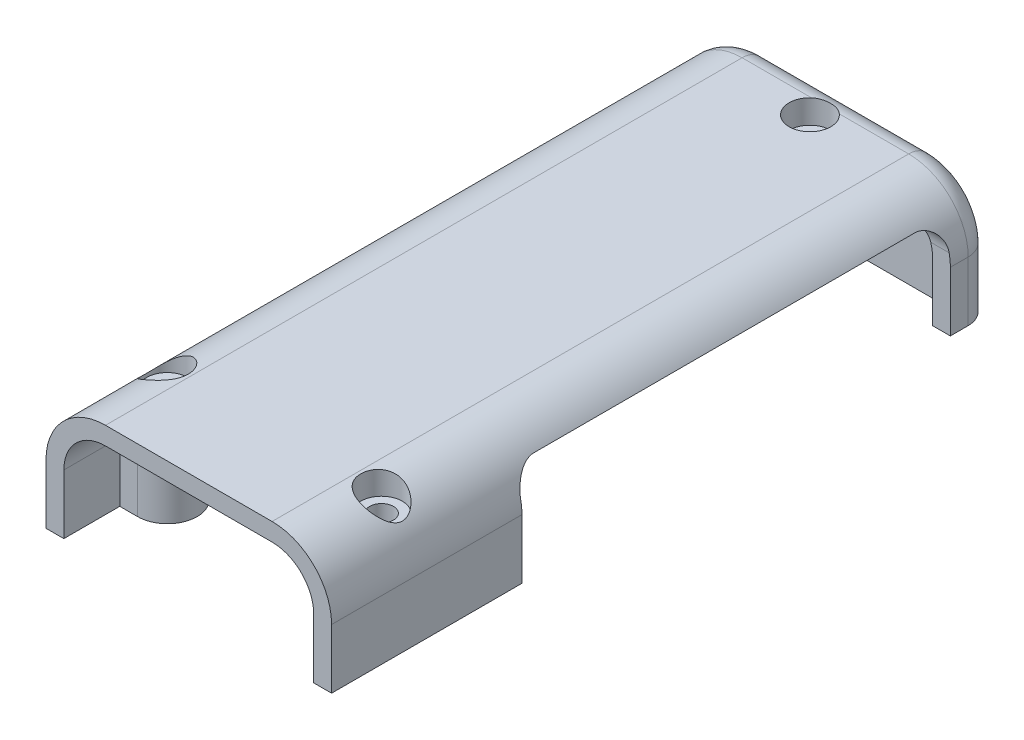
SolidWorks part; units mm, degrees
ref_plane "Front Plane" through (0, 0, 0) normal (0, 0, 1) x (1, 0, 0)
ref_plane "Top Plane" through (0, 0, 0) normal (0, 1, 0) x (1, 0, 0)
ref_plane "Right Plane" through (0, 0, 0) normal (1, 0, 0) x (0, 0, -1)
sketch "Sketch1" plane through (0, 0, 0) normal (0, 0, 1) x (1, 0, 0)
  line L0 (0, -24.4696) -> (0, 33.8552) construction
  line L1 (-46.7604, 0) -> (49.2743, 0) construction
  line L2 (10.5, 0) -> (10.5, 5)
  line L3 (12, 0) -> (12, 5)
  line L4 (-7, 8.5) -> (7, 8.5)
  line L5 (-7, 10) -> (7, 10)
  line L6 (9.2937, 5) -> (23.0317, 5) construction
  line L7 (7, 8.0974) -> (7, 12.4299) construction
  line L8 (10.5, 0) -> (12, 0)
  line L9 (-12, 0) -> (-12, 5)
  line L10 (-10.5, 0) -> (-12, 0)
  line L11 (-10.5, 0) -> (-10.5, 5)
  arc A0 (7, 8.5) -> (10.5, 5) centre (7, 5) cw
  arc A1 (7, 10) -> (12, 5) centre (7, 5) cw
  arc A2 (-7, 10) -> (-12, 5) centre (-7, 5) ccw
  arc A3 (-7, 8.5) -> (-10.5, 5) centre (-7, 5) ccw
  point P20 (0, 10)
  point P26 (0, 8.5)
  dimension "D4" = 5
  dimension "D1" = 12
  dimension "D2" = 1.5
  dimension "D3" = 10
extrude "Boss-Extrude1" add sketch "Sketch1" along normal blind 54
sketch "Sketch2" plane through (0, 0, 0) normal (0, 0, 1) x (1, 0, 0)
  line L0 (-12, 0) -> (12, 0)
  line L1 (12, 0) -> (12, 5)
  line L2 (7, 10) -> (-7, 10)
  line L3 (-12, 0) -> (-12, 5)
  arc A0 (-12, 5) -> (-7, 10) centre (-7, 5) cw
  arc A1 (12, 5) -> (7, 10) centre (7, 5) ccw
extrude "Boss-Extrude2" add sketch "Sketch2" against normal blind 1.5
sketch "Sketch3" plane through (12, 0, 0) normal (1, 0, 0) x (0, 0, -1)
  line L0 (-20, -2.8502) -> (-20, 11.6128) construction
  line L1 (-8, 0) -> (-2, 0)
  line L2 (-54, 0) -> (1.5, 0) construction
  line L3 (-2, 0) -> (-2, 6)
  line L4 (-36, 8) -> (-4, 8)
  line L5 (-38, 0) -> (-38, 6)
  line L6 (-8, 0) -> (-38, 0)
  arc A0 (-2, 6) -> (-4, 8) centre (-4, 6) ccw
  arc A1 (-38, 6) -> (-36, 8) centre (-36, 6) cw
  point P10 (-5.9016, 6.3989)
  point P11 (-8.3528, 0)
  point P14 (-20, 8)
  point P18 (-8, 0)
  dimension "D1" = 2
  dimension "D2" = 8
  dimension "D3" = 18
  dimension "D4" = 20
extrude "Cut-Extrude1" cut sketch "Sketch3" against normal blind 3
sketch "Sketch4" plane through (0, 0, 0) normal (0, -1, 0) x (1, 0, 0)
  line L0 (0, -5.1254) -> (0, 35.2905) construction
  line L1 (2.5, 0) -> (2.5, 1.8)
  line L2 (-10.5, 0) -> (10.5, 0) construction
  line L3 (-2.5, 0) -> (-2.5, 1.8)
  line L4 (-18.3062, 46.8) -> (17.3088, 46.8) construction
  line L5 (10.5, 49.3) -> (9, 49.3)
  line L6 (10.5, 54) -> (10.5, 38) construction
  line L7 (10.5, 49.3) -> (10.5, 44.3)
  line L8 (2.5, 0) -> (-2.5, 0)
  line L9 (10.5, 54) -> (10.5, 38) construction
  line L10 (10.5, 44.3) -> (9, 44.3)
  line L11 (-10.5, 49.3) -> (-10.5, 44.3)
  line L12 (-10.5, 44.3) -> (-9, 44.3)
  line L13 (-10.5, 49.3) -> (-9, 49.3)
  arc A0 (2.5, 1.8) -> (-2.5, 1.8) centre (0, 1.8) ccw
  arc A2 (9, 49.3) -> (9, 44.3) centre (9, 46.8) ccw
  arc A3 (-9, 49.3) -> (-9, 44.3) centre (-9, 46.8) cw
  point P11 (10.5, 46.8)
  point P19 (0, 0)
  dimension "D2" = 2.5
  dimension "D3" = 45
  dimension "D4" = 2.5
  dimension "D1" = 1.8
  dimension "D5" = 1.5
extrude "Boss-Extrude3" add sketch "Sketch4" against normal up to surface (8.5 mm away) up to face at (0, 8.5, 27)
sketch "Sketch5" plane through (0, 0, 0) normal (0, -1, 0) x (1, 0, 0)
  circle A0 centre (0, 1.8) radius 1
  circle A1 centre (9, 46.8) radius 1
  circle A2 centre (-9, 46.8) radius 1
  dimension "D1" = 2
extrude "Cut-Extrude2" cut sketch "Sketch5" against normal up to surface (10 mm away) up to face at (0, 10, 26.25)
sketch "Sketch6" plane through (0, 10, 0) normal (0, 1, 0) x (1, 0, 0)
  point P0 (0, -1.8)
  point P1 (-9, -46.8)
  point P3 (9, -46.8)
hole_wizard "Hole1" positions "Sketch7" profile "Sketch8" legacy end condition through all
sketch "Sketch7" plane through (0, 10, 0) normal (0, 1, 0) x (1, 0, 0)
  point P0 (0, -1.8)
  point P3 (-9, -46.8)
  point P6 (9, -46.8)
sketch "Sketch8" plane through (0, 10, 1.8) normal (1, 0, 0) x (0, 0, 1)
  line L0 (0, 0) -> (0, 10)
  line L1 (0, 10) -> (1, 10)
  line L2 (1, 10) -> (1, 2)
  line L3 (1, 2) -> (1.75, 2)
  line L4 (1.75, 2) -> (1.75, 0)
  line L5 (1.75, 0) -> (0, 0)
  line L6 (0, 110) -> (0, -10) construction
  dimension "Diameter" = 2
  dimension "Depth" = 10
  dimension "C-Bore Diameter" = 3.5
  dimension "C-Bore Depth" = 2
sketch "Sketch10" plane through (-12, 0, 0) normal (-1, 0, 0) x (0, 0, 1)
  line L0 (8, -3.4314) -> (8, 15.5314) construction
  line L1 (4, 0) -> (4, 4)
  line L2 (54, 0) -> (-1.5, 0) construction
  line L3 (10, 6) -> (6, 6)
  line L4 (4, 0) -> (12, 0)
  line L5 (12, 0) -> (12, 4)
  line L6 (0, -3.2088) -> (0, 12.5587) construction
  arc A0 (4, 4) -> (6, 6) centre (6, 4) cw
  arc A1 (12, 4) -> (10, 6) centre (10, 4) ccw
  point P11 (8, 6)
  point P14 (8, 0)
  dimension "D2" = 2
  dimension "D1" = 4
  dimension "D3" = 6
  dimension "D4" = 8
extrude "Cut-Extrude4" cut sketch "Sketch10" against normal blind 3
fillet "Fillet1" radius 2 5 edges at (12, 2.5, -1.5) (10.5355, 8.5355, -1.5) (-12, 2.5, -1.5) (-10.5355, 8.5355, -1.5) (0, 10, -1.5)
